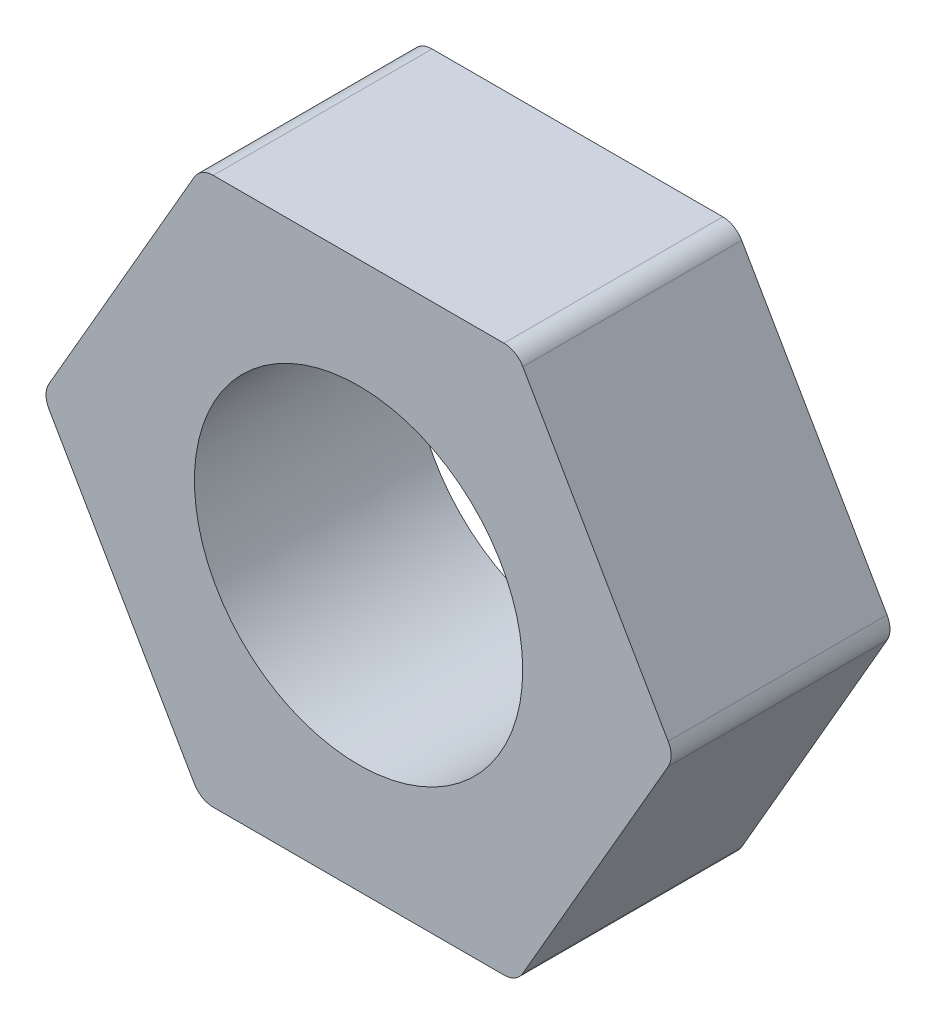
SolidWorks part; units mm, degrees
ref_plane "Front Plane" through (0, 0, 0) normal (0, 0, 1) x (1, 0, 0)
ref_plane "Top Plane" through (0, 0, 0) normal (0, 1, 0) x (1, 0, 0)
ref_plane "Right Plane" through (0, 0, 0) normal (1, 0, 0) x (0, 0, -1)
sketch "Sketch2" plane through (0, 0, 0) normal (0, 0, 1) x (1, 0, 0)
  line L1 (488.5803, 2) -> (462.0222, 48)
  line L2 (458.5581, 50) -> (405.4419, 50)
  line L3 (401.9778, 48) -> (375.4197, 2)
  line L4 (375.4197, -2) -> (401.9778, -48)
  line L5 (405.4419, -50) -> (458.5581, -50)
  line L6 (462.0222, -48) -> (488.5803, -2)
  circle A0 centre (432, 0) radius 50 construction
  arc A1 (458.5581, -50) -> (462.0222, -48) centre (458.5581, -46) ccw
  arc A2 (401.9778, -48) -> (405.4419, -50) centre (405.4419, -46) ccw
  arc A3 (375.4197, 2) -> (375.4197, -2) centre (378.8838, 0) ccw
  arc A4 (405.4419, 50) -> (401.9778, 48) centre (405.4419, 46) ccw
  arc A5 (462.0222, 48) -> (458.5581, 50) centre (458.5581, 46) ccw
  arc A6 (488.5803, 2) -> (488.5803, -2) centre (485.1162, 0) cw
  circle M7 centre (432, 0) radius 30
  dimension "D1" = 100
  dimension "D2" = 4
extrude "Boss-Extrude1" add sketch "Sketch2" along normal blind 40 contours L5 L6 L1 L2 L3 L4 M7 region at (487.598, 0, 0)
